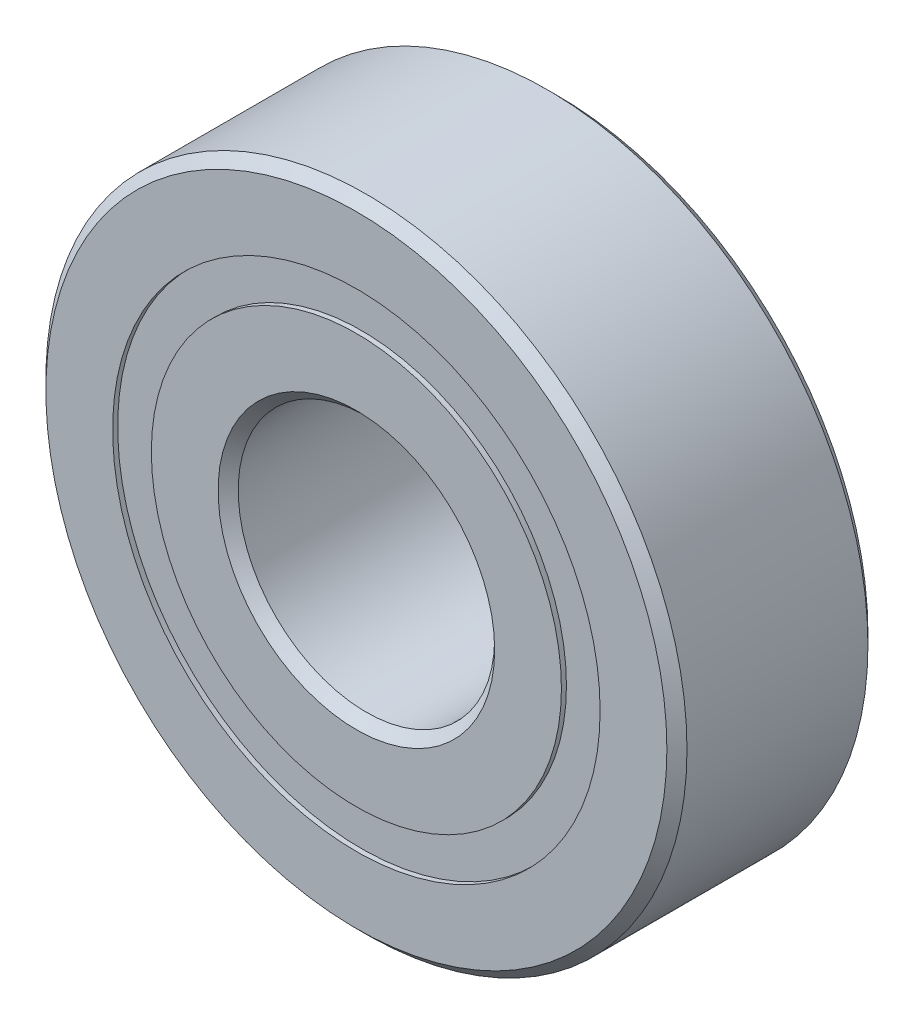
SolidWorks part; units mm, degrees
ref_plane "Front Plane" through (0, 0, 0) normal (0, 0, 1) x (1, 0, 0)
ref_plane "Top Plane" through (0, 0, 0) normal (0, 1, 0) x (1, 0, 0)
ref_plane "Right Plane" through (0, 0, 0) normal (1, 0, 0) x (0, 0, -1)
sketch "Sketch1" plane through (0, 0, 0) normal (1, 0, 0) x (0, 0, -1)
  line L0 (-2.4892, 0) -> (2.4892, 0) construction
  line L1 (0, 7.9375) -> (0, -7.9375) construction
  line L2 (2.2403, 7.9375) -> (-2.2403, 7.9375)
  line L3 (-2.2403, 7.9375) -> (-2.4892, 7.6886)
  line L4 (-2.4892, 7.6886) -> (-2.4892, 6.0352)
  line L5 (-2.4892, 6.0352) -> (-1.1063, 6.0352)
  line L6 (2.4892, 6.0352) -> (1.1063, 6.0352)
  line L7 (2.4892, 7.6886) -> (2.4892, 6.0352)
  line L8 (2.2403, 7.9375) -> (2.4892, 7.6886)
  line L9 (0, 7.9375) -> (0, 5.5563) construction
  line L10 (0, 5.5563) -> (0, 3.175) construction
  arc A0 (-1.1063, 6.0352) -> (1.1063, 6.0352) centre (0, 5.5563) cw
  point P14 (0, 3.175)
  dimension "Width" = 4.9784
  dimension "OD" = 15.875
  dimension "D1" = 45
  dimension "D2" = 0.2489
  dimension "D3" = 2.2126
  dimension "D4" = 0.479
revolve "Revolve1" add sketch "Sketch1" angle 360 about L0
sketch "Sketch3" plane through (0, 0, 0) normal (1, 0, 0) x (0, 0, -1)
  line L0 (-1.1063, 5.0773) -> (-2.4892, 5.0773)
  line L1 (-2.4892, 7.6886) -> (-2.4892, 6.0352) construction
  line L2 (-2.2403, 7.9375) -> (-2.4892, 7.6886) construction
  line L3 (-2.4892, 5.0773) -> (-2.4892, 3.4239)
  line L5 (-2.4892, 3.4239) -> (-2.2403, 3.175)
  line L6 (-2.2403, 3.175) -> (2.2403, 3.175)
  line L7 (2.2403, 7.9375) -> (2.2403, -7.9375) construction
  line L8 (2.2403, 3.175) -> (2.4892, 3.4239)
  line L9 (2.4892, -7.6886) -> (2.4892, 7.6886) construction
  line L10 (2.4892, 3.4239) -> (2.4892, 5.0773)
  line L11 (2.4892, 5.0773) -> (1.1063, 5.0773)
  line L12 (0, 7.9375) -> (0, -7.9375) construction
  line L13 (2.2403, 7.9375) -> (2.4892, 7.6886) construction
  arc A1 (1.1063, 5.0773) -> (-1.1063, 5.0773) centre (0, 5.5562) cw
  arc A2 (1.1063, 6.0352) -> (-1.1063, 6.0352) centre (0, 5.5563) ccw construction
revolve "Revolve3" add sketch "Sketch3" angle 360 about L0
sketch "Sketch4" plane through (0, 0, 0) normal (1, 0, 0) x (0, 0, -1)
  line L0 (-1.2055, 5.5563) -> (1.2055, 5.5563)
  arc A2 (-1.2055, 5.5563) -> (1.2055, 5.5563) centre (0, 5.5563) cw
  arc A3 (1.1063, 6.0352) -> (-1.1063, 6.0352) centre (0, 5.5563) ccw construction
revolve "Revolve4" add sketch "Sketch4" angle 360 about L0
ref_axis "Axis1" through (0, 0, -2.4892) along (0, 0, 1)
pattern_circular "CirPattern1" count 12 every 30 about axis through (0, 0, -2.4892) along (0, 0, 1) of bodies 104
sketch "Sketch5" plane through (0, 0, 0) normal (1, 0, 0) x (0, 0, -1)
  line L0 (-2.4892, 6.0352) -> (-1.1063, 6.0352) construction
  line L1 (-2.3647, 6.0352) -> (-1.2055, 6.0352)
  line L2 (-2.3647, 6.0352) -> (-2.3647, 5.0773)
  line L3 (-2.3647, 5.0773) -> (-1.2055, 5.0773)
  line L4 (-1.2055, 6.0352) -> (-1.2055, 5.0773)
  line L5 (-1.1063, 5.0773) -> (-2.4892, 5.0773) construction
  line L6 (2.4892, 6.0352) -> (1.1063, 6.0352) construction
  line L7 (2.3647, 6.0352) -> (1.2055, 6.0352)
  line L8 (2.3647, 6.0352) -> (2.3647, 5.0773)
  line L9 (2.3647, 5.0773) -> (1.2055, 5.0773)
  line L10 (1.2055, 6.0352) -> (1.2055, 5.0773)
  line L11 (2.4892, 5.0773) -> (1.1063, 5.0773) construction
  line L12 (-2.2403, 7.9375) -> (-2.4892, 7.6886) construction
  point P18 (-2.3647, 7.813)
revolve "Revolve5" add sketch "Sketch5" angle 360 about L0
equation "\"D2@Sketch1\" = \"Width@Sketch1\"*.05"
equation "\"D3@Sketch1\" = \"Width@Sketch1\"/2.25"
equation "\"D4@Sketch1\" = (((\"OD@Sketch1\"-\"Width@Sketch1\")/2)/3.25)/3.5"
equation "\"D2@CirPattern1\" = 360/\"Balls@CirPattern1\""
